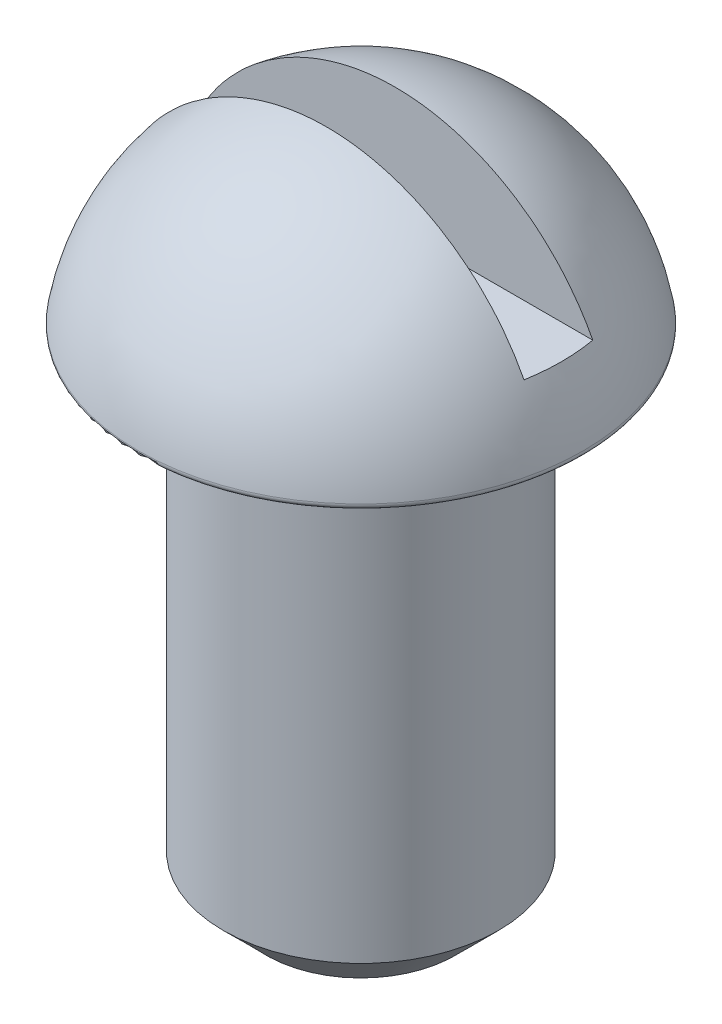
SolidWorks part; units mm, degrees
ref_plane "Спереди" through (0, 0, 0) normal (0, 0, 1) x (1, 0, 0)
ref_plane "Сверху" through (0, 0, 0) normal (0, 1, 0) x (1, 0, 0)
ref_plane "Справа" through (0, 0, 0) normal (1, 0, 0) x (0, 0, -1)
sketch "Эскиз1" plane through (0, 0, 0) normal (0, 0, 1) x (1, 0, 0)
  line L0 (0, 125.7632) -> (0, 0) construction
  line L1 (4, 88.6493) -> (6.5, 88.6493)
  line L2 (0, 94.2493) -> (0, 74.2493)
  line L3 (0, 94.2493) -> (1, 94.2493)
  line L4 (4, 88.6493) -> (4, 74.2493)
  line L6 (4, 74.2493) -> (0, 74.2493)
  arc A0 (1, 94.2493) -> (6.5, 88.6493) centre (-0.0358, 87.7311) cw
  dimension "D1" = 1
  dimension "D2" = 5.6
  dimension "D3" = 20
  dimension "D4" = 6.6
  dimension "D5" = 4
  dimension "D6" = 6.5
revolve "Повернуть1" add sketch "Эскиз1" angle 360 about L0
ref_axis "Ось4" through (0, 0.9334, 0) along (0, -1, 0)
sketch "Эскиз13" plane through (0, 94.2493, 0) normal (0, 1, 0) x (-1, 0, 0)
  line L1 (6.5, -1) -> (-6.5, -1)
  line L2 (6.5, -1) -> (6.5, 1)
  line L3 (6.5, 1) -> (-6.5, 1)
  line L4 (-6.5, -1) -> (-6.5, 1)
  dimension "D1" = 6.5
  dimension "D2" = 13
  dimension "D3" = 1
  dimension "D4" = 2
extrude "Вырез-Вытянуть9" cut sketch "Эскиз13" against normal blind 3.5
fillet "Скругление1" radius 0.15 1 edges at (-6.5, 88.6493, 0)
chamfer "Фаска1" distance 1.25 angle 45 1 edges at (-4, 74.2493, 0)
